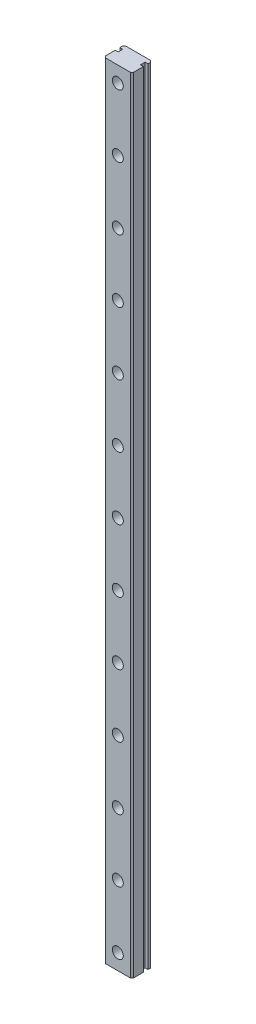
SolidWorks part; units mm, degrees
material "AISI 304"
ref_plane "前视基准面" through (0, 0, 0) normal (0, 0, 1) x (1, 0, 0)
ref_plane "上视基准面" through (0, 0, 0) normal (0, 1, 0) x (1, 0, 0)
ref_plane "右视基准面" through (0, 0, 0) normal (1, 0, 0) x (0, 0, -1)
sketch "草图1" plane through (0, 0, 0) normal (0, 1, 0) x (1, 0, 0)
  line L1 (-4.5, -3.25) -> (4.5, -3.25)
  line L2 (-4.5, -3.25) -> (-4.5, 3.25)
  line L3 (-4.5, 3.25) -> (4.5, 3.25)
  line L4 (4.5, -3.25) -> (4.5, 3.25)
  line L5 (-4.5, -3.25) -> (4.5, 3.25) construction
  line L6 (-4.5, 3.25) -> (4.5, -3.25) construction
  point P0 (0, 0)
  dimension "D1" = 9
  dimension "D2" = 6.5
extrude "凸台-拉伸1" add sketch "草图1" along normal blind 125 and the other way blind 125
sketch "草图2" plane through (0, 0, 0) normal (0, 1, 0) x (1, 0, 0)
  line L0 (0, 0) -> (4.5, 0) construction
  line L1 (4.5, -3.25) -> (4.5, 3.25) construction
  line L2 (0, 0) -> (0, 3.25) construction
  line L3 (4.5, 3.25) -> (-4.5, 3.25) construction
  line L4 (4.5, 1.89) -> (3.55, 1.89)
  line L5 (3.55, 1.89) -> (3.55, 0.41)
  line L6 (3.55, 0.41) -> (4.5, 0.41)
  line L7 (4.5, 1.89) -> (4.5, 0.41)
  line L8 (-3.55, 0.41) -> (-4.5, 0.41)
  line L9 (-3.55, 1.89) -> (-3.55, 0.41)
  line L10 (-4.5, 1.89) -> (-3.55, 1.89)
  line L11 (-4.5, 1.89) -> (-4.5, 0.41)
  dimension "D1" = 0.95
  dimension "D2" = 1.48
  dimension "D3" = 1.36
extrude "切除-拉伸1" cut sketch "草图2" against normal blind 125 and the other way blind 125
chamfer "倒角2" distance 0.5 angle 45 4 edges at (-4.5, 0, 3.25) (4.5, 0, 3.25) (4.5, 0, -3.25) (-4.5, 0, -3.25)
sketch "草图3" plane through (0, 0, -3.25) normal (0, 0, -1) x (-1, 0, 0)
  line L0 (0, 0) -> (0, -137.3682) construction
  line L1 (-4, -125) -> (4, -125) construction
  line L2 (4.5, 125) -> (4.5, -125) construction
  circle A0 centre (0, -120) radius 3
  circle A1 centre (0, -100) radius 3
  circle A2 centre (0, -80) radius 3
  circle A3 centre (0, -60) radius 3
  circle A4 centre (0, -40) radius 3
  circle A5 centre (0, -20) radius 3
  circle A6 centre (0, 0) radius 3
  circle A7 centre (0, 20) radius 3
  circle A8 centre (0, 40) radius 3
  circle A9 centre (0, 60) radius 3
  circle A10 centre (0, 80) radius 3
  circle A11 centre (0, 100) radius 3
  circle A12 centre (0, 120) radius 3
  dimension "D1" = 6
  dimension "D5" = 6
  dimension "D2" = 5
  dimension "D4" = 20
  dimension "D6" = 20
  dimension "D7" = 4.5
  dimension "D3" = 12
extrude "切除-拉伸2" cut sketch "草图3" against normal blind 3.5
sketch "草图4" plane through (0, 0, 0.25) normal (0, 0, -1) x (-1, 0, 0)
  line L0 (0, 0) -> (0, 21.8734) construction
  circle A0 centre (0, -120) radius 1.75
  circle A1 centre (0, -100) radius 1.75
  circle A2 centre (0, -80) radius 1.75
  circle A3 centre (0, -60) radius 1.75
  circle A4 centre (0, -40) radius 1.75
  circle A5 centre (0, -20) radius 1.75
  circle A6 centre (0, 0) radius 1.75
  circle A7 centre (0, 20) radius 1.75
  circle A8 centre (0, 40) radius 1.75
  circle A9 centre (0, 60) radius 1.75
  circle A10 centre (0, 80) radius 1.75
  circle A11 centre (0, 100) radius 1.75
  circle A12 centre (0, 120) radius 1.75
  circle A13 centre (0, 140) radius 1.75
  circle A14 centre (0, 160) radius 1.75
  dimension "D1" = 3.5
  dimension "D3" = 20
  dimension "D2" = 15
extrude "切除-拉伸3" cut sketch "草图4" against normal blind 5
